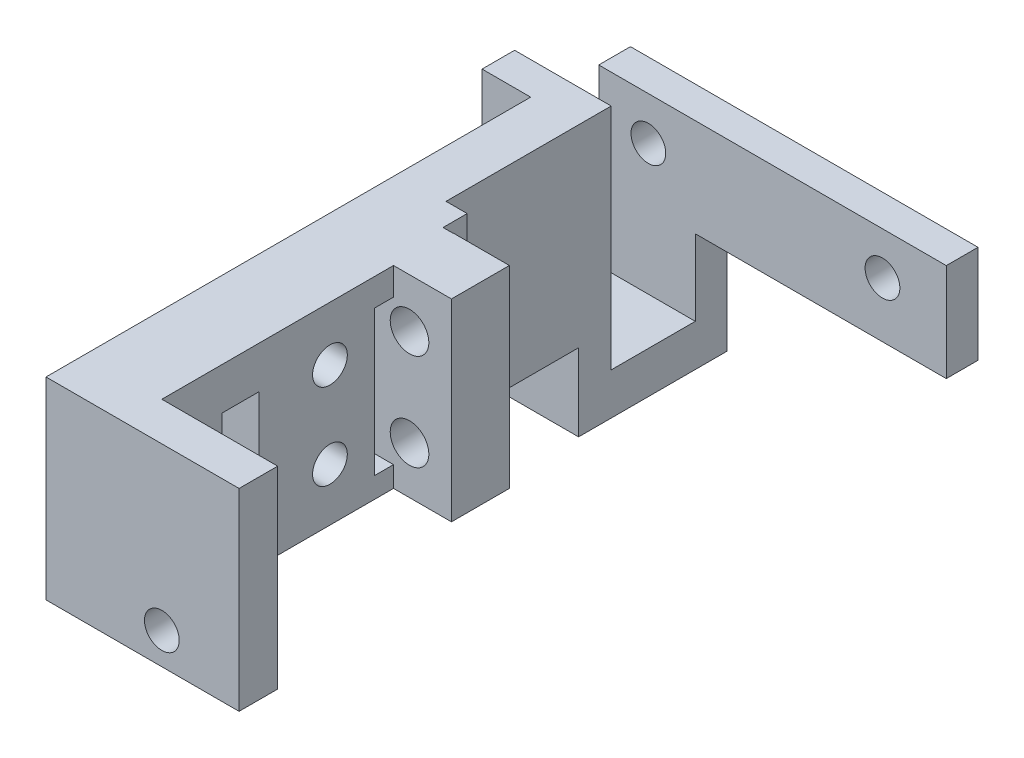
SolidWorks part; units mm, degrees
ref_plane "Front" through (0, 0, 0) normal (0, 0, 1) x (1, 0, 0)
ref_plane "Top" through (0, 0, 0) normal (0, 1, 0) x (1, 0, 0)
ref_plane "Right" through (0, 0, 0) normal (1, 0, 0) x (0, 0, -1)
sketch "Sketch1" plane through (0, 0, 0) normal (0, 1, 0) x (1, 0, 0)
  line L1 (0, 0) -> (8, 0)
  line L2 (0, 0) -> (0, -56.58)
  line L3 (0, -56.58) -> (8, -56.58)
  line L4 (8, 0) -> (8, -56.58)
  line L5 (0, -26.58) -> (14, -26.58)
  line L6 (0, -26.58) -> (0, -32.58)
  line L7 (0, -32.58) -> (14, -32.58)
  line L8 (14, -26.58) -> (14, -32.58)
  line L9 (0, -56.58) -> (20, -56.58)
  line L10 (0, -56.58) -> (0, -60.58)
  line L11 (0, -60.58) -> (20, -60.58)
  line L12 (20, -56.58) -> (20, -60.58)
  dimension "D1" = 24
  dimension "D2" = 6
  dimension "D3" = 6
  dimension "D4" = 8
  dimension "D5" = 4
  dimension "D6" = 20
  dimension "D7" = 56.58
extrude "Boss-Extrude1" add sketch "Sketch1" along normal blind 20 contours L7 L2 L3 L4 | L2 L7 L4 L5 | L2 L5 L4 L1 | L8 L5 L4 L7 | L12 L9 L3 L10 L11 region at (4, 0, 13.29) region at (4, 0, 29.58) region at (11, 0, 29.58) region at (4, 0, 44.58) region at (10, 0, 58.58)
sketch "Sketch2" plane through (0, 0, 0) normal (0, -1, 0) x (-1, 0, 0)
  line L0 (-7.4058, -24.1058) -> (-8.9058, -24.1058) construction
  line L1 (-8.1558, -24.1058) -> (-5.3536, -24.1058)
  line L2 (-8.1558, -24.1058) -> (-8.1558, 0.2442)
  line L3 (-8.1558, 0.2442) -> (-5.3536, 0.2442)
  line L4 (-5.3536, -24.1058) -> (-5.3536, 0.2442)
  line L6 (-8.1558, -24.1058) -> (-7.1558, -24.1058)
  line L7 (-8.1558, -24.1058) -> (-8.1558, -26.6058)
  line L8 (-8.1558, -26.6058) -> (-7.1558, -26.6058)
  line L9 (-7.1558, -24.1058) -> (-7.1558, -26.6058)
  line L10 (-5.3536, 0.2442) -> (-4.9638, 0.2442)
  line L11 (-5.3536, 0.2442) -> (-5.3536, -24.1058)
  line L12 (-5.3536, -24.1058) -> (-4.9638, -24.1058)
  line L13 (-4.9638, 0.2442) -> (-4.9638, -24.1058)
  line M6 (0, 0) -> (-8, 0)
  line M7 (-8, 0) -> (-8, -26.58)
  line M8 (-8, -26.58) -> (-14, -26.58)
  dimension "D1" = 2.5
  dimension "D2" = 1
extrude "Cut-Extrude1" cut sketch "Sketch2" against normal blind 20 contours L9 L1 L7 L8 M7 M8 | L1 L4 M6 M7 | L13 L4 L12 M6 region at (6.6768, 0, 12.0529) region at (7.5789, 0, 25.3582) region at (5.1587, 0, 12.0529)
sketch "Sketch3" plane through (0, 0, 0) normal (0, 0, -1) x (-1, 0, 0)
  line L1 (19.612, -22.3932) -> (-22.8928, -22.3932)
  line L2 (19.612, -22.3932) -> (19.612, 38.8779)
  line L3 (19.612, 38.8779) -> (-22.8928, 38.8779)
  line L4 (-22.8928, -22.3932) -> (-22.8928, 38.8779)
extrude "Cut-Extrude2" cut sketch "Sketch3" against normal blind 7
sketch "Sketch5" plane through (0, 0, 0) normal (0, -1, 0) x (-1, 0, 0)
  line L1 (-4.9638, -7) -> (5.0362, -7)
  line L2 (-4.9638, -7) -> (-4.9638, -10.373)
  line L3 (-4.9638, -10.373) -> (5.0362, -10.373)
  line L4 (5.0362, -7) -> (5.0362, -10.373)
extrude "Boss-Extrude3" add sketch "Sketch5" against normal blind 20 and the other way blind 8
sketch "Sketch6" plane through (0, 0, 26.58) normal (0, 0, -1) x (-1, 0, 0)
  circle A0 centre (-9.6558, 4.9046) radius 2
  circle A1 centre (-9.6558, 14.9046) radius 2
extrude "Cut-Extrude3" cut sketch "Sketch6" against normal blind 6
sketch "Sketch7" plane through (0, 0, 7) normal (0, 0, -1) x (-1, 0, 0)
  line L0 (5.0362, -8) -> (5.0362, 20) construction
  line L1 (-4.9638, -8) -> (5.0362, -8)
  line L2 (-4.9638, -8) -> (-4.9638, -3.6743)
  line L3 (-4.9638, -3.6743) -> (5.0362, -3.6743)
  line L4 (5.0362, -8) -> (5.0362, -3.6743)
extrude "Boss-Extrude4" add sketch "Sketch7" along normal blind 12
sketch "Sketch8" plane through (0, -3.6743, 0) normal (0, 1, 0) x (1, 0, 0)
  line L0 (-5.0362, 5) -> (-5.0362, -7) construction
  line L1 (4.9638, 5) -> (-5.0362, 5)
  line L2 (4.9638, 5) -> (4.9638, 1.7149)
  line L3 (4.9638, 1.7149) -> (-5.0362, 1.7149)
  line L4 (-5.0362, 5) -> (-5.0362, 1.7149)
extrude "Boss-Extrude5" add sketch "Sketch8" along normal blind 18
sketch "Sketch9" plane through (0, 0, -5) normal (0, 0, -1) x (-1, 0, 0)
  circle A0 centre (-0.1027, 9.8606) radius 1.8
extrude "Cut-Extrude4" cut sketch "Sketch9" against normal blind 20
sketch "Sketch10" plane through (0, 0, 0) normal (-1, 0, 0) x (0, 0, 1)
  line L0 (10.373, 0) -> (10.373, 8.0635) construction
  line L1 (10.373, 7) -> (15.0312, 7)
  line L2 (10.373, 7) -> (10.373, 12.7)
  line L3 (10.373, 12.7) -> (15.0312, 12.7)
  line L4 (15.0312, 7) -> (15.0312, 12.7)
  line L5 (10.373, 0) -> (60.58, 0) construction
  dimension "D1" = 5.7
  dimension "D2" = 7
extrude "Cut-Extrude5" cut sketch "Sketch10" against normal blind 3
sketch "Sketch12" plane through (0, 0, 60.58) normal (0, 0, 1) x (1, 0, 0)
  line L0 (20, 20) -> (20, 0) construction
  circle A0 centre (12, 3.2655) radius 1.8
  dimension "D1" = 8
extrude "Cut-Extrude7" cut sketch "Sketch12" against normal blind 5
sketch "Sketch13" plane through (0, 0, 0) normal (-1, 0, 0) x (0, 0, 1)
  circle A0 centre (39.1672, 5.4688) radius 1.8
  circle A1 centre (39.1672, 14.3708) radius 1.8
extrude "Cut-Extrude8" cut sketch "Sketch13" against normal blind 12
sketch "Sketch14" plane through (4.9638, 0, 0) normal (1, 0, 0) x (0, 0, -1)
  line L0 (5, 14.3257) -> (5, -8) construction
  line L1 (1.7149, 14.3257) -> (5, 14.3257)
  line L2 (1.7149, 14.3257) -> (1.7149, 4.185)
  line L3 (1.7149, 4.185) -> (5, 4.185)
  line L4 (5, 14.3257) -> (5, 4.185)
extrude "Boss-Extrude6" add sketch "Sketch14" along normal blind 26
sketch "Sketch15" plane through (0, 0, -5) normal (0, 0, -1) x (-1, 0, 0)
  circle A0 centre (-24.3532, 9.9046) radius 1.8
extrude "Cut-Extrude9" cut sketch "Sketch15" against normal blind 20
sketch "Sketch16" plane through (8, 0, 0) normal (1, 0, 0) x (0, 0, -1)
  line L0 (-32.58, 20) -> (-32.58, 16.0264) construction
  line L1 (-32.58, 17.1649) -> (-34.5527, 17.1649)
  line L2 (-32.58, 17.1649) -> (-32.58, 2.1366)
  line L3 (-32.58, 2.1366) -> (-34.5527, 2.1366)
  line L4 (-34.5527, 17.1649) -> (-34.5527, 2.1366)
extrude "Cut-Extrude10" cut sketch "Sketch16" against normal blind 2
sketch "Sketch18" plane through (0, 0, 0) normal (-1, 0, 0) x (0, 0, 1)
  line L1 (46.5401, 4.9513) -> (50.3649, 4.9513)
  line L2 (46.5401, 4.9513) -> (46.5401, 15.6436)
  line L3 (46.5401, 15.6436) -> (50.3649, 15.6436)
  line L4 (50.3649, 4.9513) -> (50.3649, 15.6436)
extrude "Cut-Extrude11" cut sketch "Sketch18" against normal blind 10
